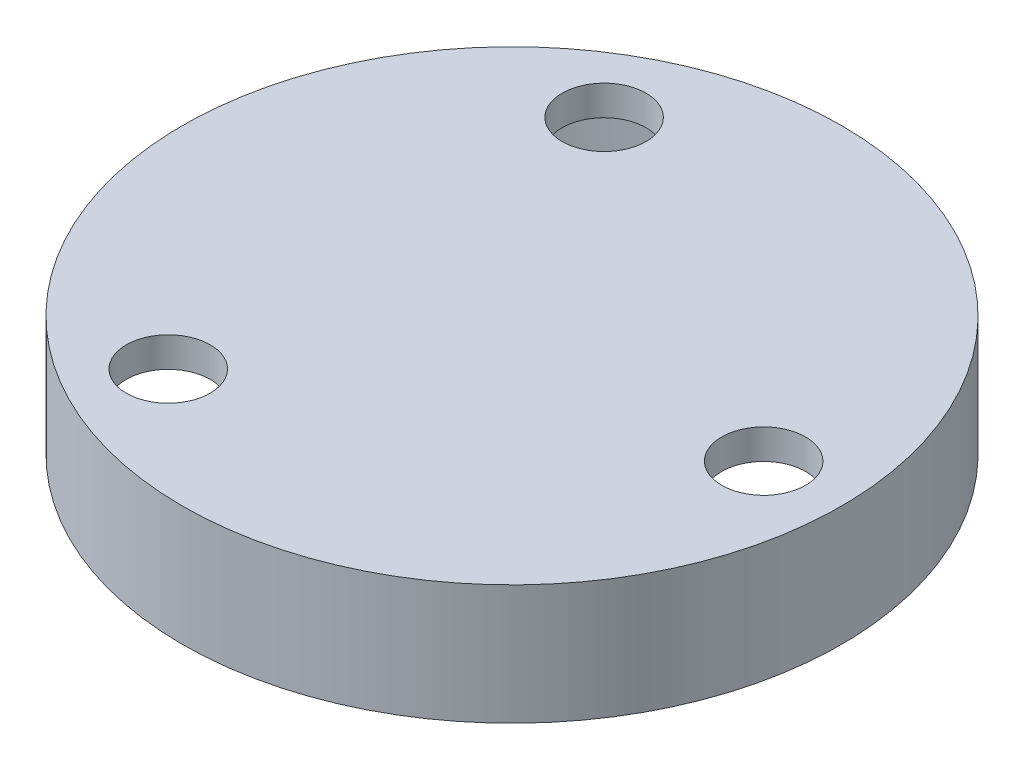
SolidWorks part; units mm, degrees
ref_plane "Front Plane" through (0, 0, 0) normal (0, 0, 1) x (1, 0, 0)
ref_plane "Top Plane" through (0, 0, 0) normal (0, 1, 0) x (1, 0, 0)
ref_plane "Right Plane" through (0, 0, 0) normal (1, 0, 0) x (0, 0, -1)
sketch "Sketch2" plane through (0, 0, 0) normal (0, 1, 0) x (1, 0, 0)
  circle A0 centre (0, 0) radius 55
  circle A1 centre (0, 0) radius 50
  dimension "D1" = 110
  dimension "D2" = 100
extrude "Boss-Extrude1" add sketch "Sketch2" against normal blind 20
ref_axis "Axis1" through (0, -21, 0) along (0, 1, 0)
sketch "Sketch3" plane through (0, 0, 0) normal (0, 1, 0) x (1, 0, 0)
  circle A0 centre (0, 0) radius 55
  point P4 (0, 0)
  dimension "D1" = 110
extrude "Boss-Extrude2" add sketch "Sketch3" against normal blind 5
sketch "Sketch5" plane through (0, 0, 0) normal (0, 1, 0) x (1, 0, 0)
  circle A0 centre (0, 0) radius 42
  point P3 (42, 0)
  dimension "D1" = 84
hole_wizard "Tap Drill for M14x2.0 Tap1" positions "Sketch5" profile "Sketch6" hole size "M14x2.0" standard "ANSI Metric" end condition through all
sketch "Sketch6" plane through (42, 0, 0) normal (1, 0, 0) x (0, 0, 1)
  line L0 (0, 0) -> (0, 20)
  line L1 (0, 20) -> (7, 20)
  line L2 (7, 20) -> (7, 0)
  line L5 (7, 0) -> (0, 0)
  line L11 (0, -6.35) -> (0, 107.95) construction
  dimension "Thru Hole Dia." = 14
  dimension "Thru Hole Depth" = 20
pattern_circular "CirPattern1" count 3 over 360 about axis through (0, -21, 0) along (0, 1, 0) of "Tap Drill for M14x2.0 Tap1"
